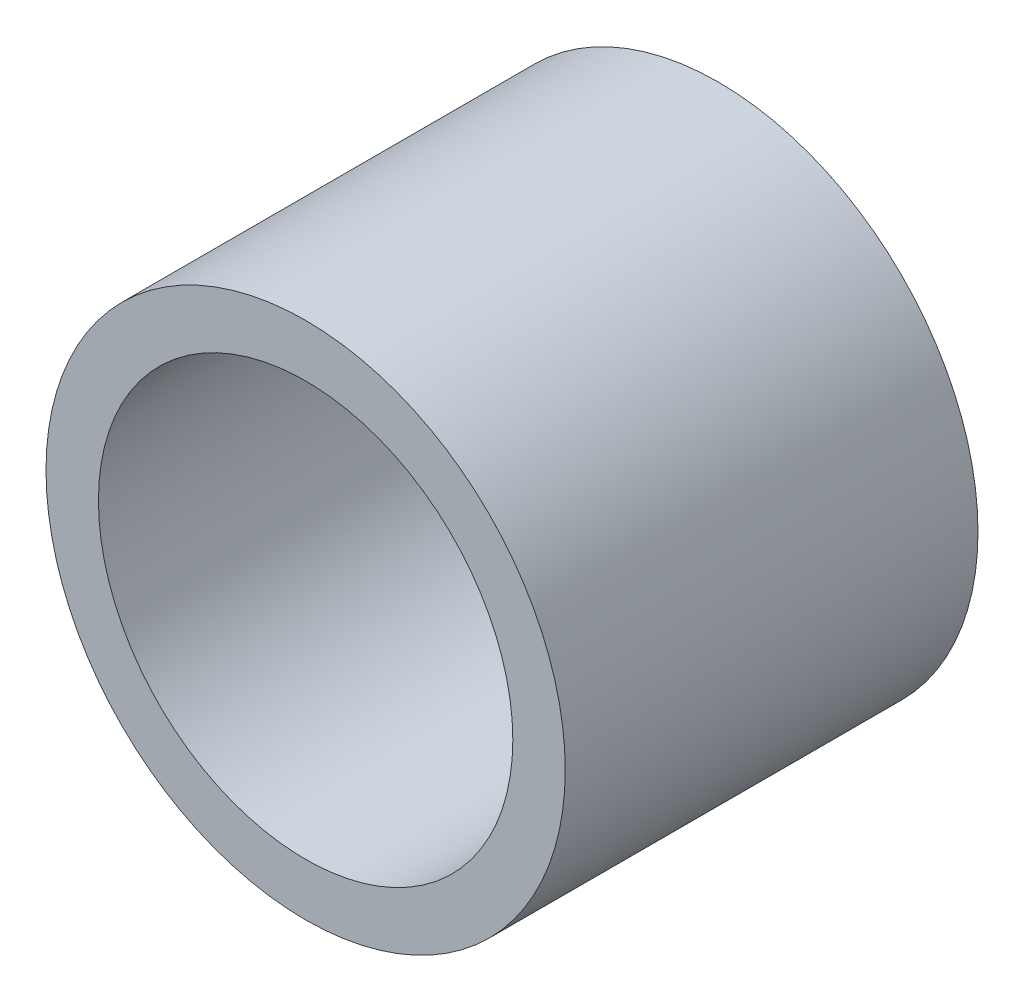
SolidWorks part; units mm, degrees
material "Tin Bearing Bronze"
ref_plane "Front Plane" through (0, 0, 0) normal (0, 0, 1) x (1, 0, 0)
ref_plane "Top Plane" through (0, 0, 0) normal (0, 1, 0) x (1, 0, 0)
ref_plane "Right Plane" through (0, 0, 0) normal (1, 0, 0) x (0, 0, -1)
sketch "Sketch1" plane through (0, 0, 0) normal (0, 0, 1) x (1, 0, 0)
  circle A0 centre (0, 0) radius 3.9942
  circle A1 centre (0, 0) radius 3.1877
  dimension "OD" = 7.9883
  dimension "ID" = 6.3754
sketch "Sketch2" plane through (0, 0, 0) normal (1, 0, 0) x (0, 0, -1)
  line L2 (3.175, 0) -> (-3.175, 0) construction
  line L4 (-3.175, -3.9942) -> (-3.175, 3.9941) construction
  line L5 (-3.175, -3.1877) -> (3.175, -3.1877)
  line L6 (3.175, 3.1877) -> (-3.175, 3.1877)
  line L7 (3.175, -3.9942) -> (3.175, 3.9941) construction
  line L8 (-3.175, 3.9941) -> (3.175, 3.9941) construction
  line L9 (-3.175, -3.9942) -> (3.175, -3.9942) construction
  line L10 (0, 3.9942) -> (0, -3.9942) construction
  line L11 (0, 3.1877) -> (0, -3.1877) construction
  point P4 (0, -3.1877)
  point P7 (0, 3.1877)
  point P8 (0, 0)
  point P12 (-3.175, 0)
  point P15 (3.175, 0)
  point P16 (0, -3.9942)
  point P17 (0, 3.9942)
  dimension "Length" = 6.35
sketch "Sketch5" plane through (0, 0, 0) normal (0, 0, 1) x (1, 0, 0)
  circle A1 centre (0, 0) radius 3.1877
  circle A2 centre (0, 0) radius 3.1877
  circle A3 centre (0, 0) radius 3.9942
  circle A4 centre (0, 0) radius 3.9942
  dimension "D1" = 0
  dimension "D2" = 0
extrude "Boss-Extrude1" add sketch "Sketch5" along normal up to vertex (3.175 mm away) and the other way up to vertex (3.175 mm away) up to point (0, 0, 3.175) other way up to point (0, 0, -3.175)
sketch "Sketch4" plane through (0, 0, 3.175) normal (0, 0, 1) x (1, 0, 0)
  line L0 (0, 0) -> (-2.254, 2.254)
  line L2 (0, -3.9942) -> (0, 3.9941) construction
  circle A1 centre (0, 0) radius 3.1877 construction
  dimension "D1" = 45
equation "\"D1\"= \"Length@Sketch2\""
